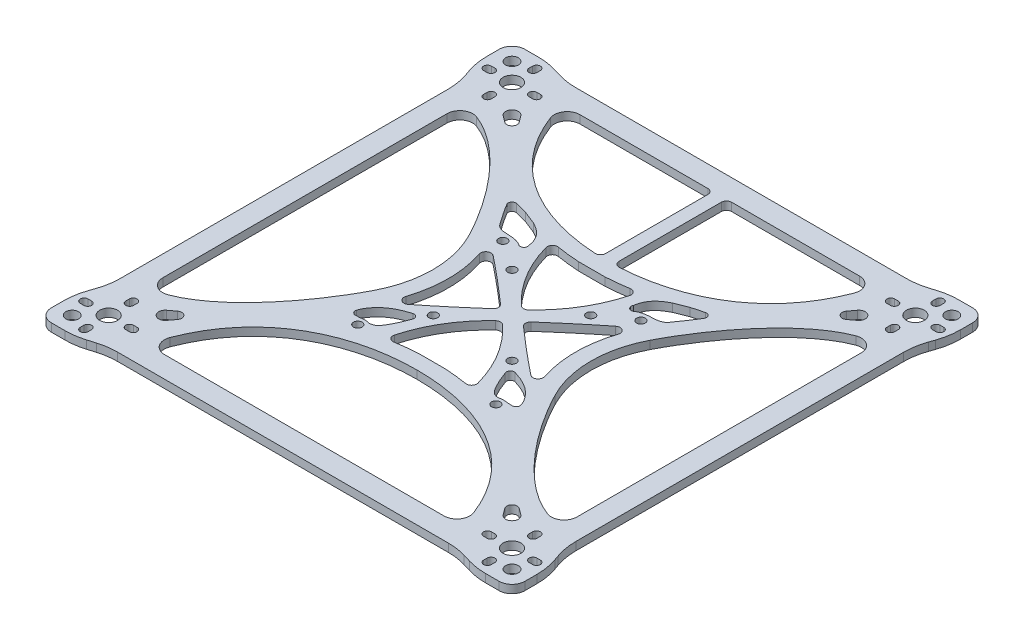
SolidWorks part; units mm, degrees
ref_plane "Front Plane" through (0, 0, 0) normal (0, 0, 1) x (1, 0, 0)
ref_plane "Top Plane" through (0, 0, 0) normal (0, 1, 0) x (1, 0, 0)
ref_plane "Right Plane" through (0, 0, 0) normal (1, 0, 0) x (0, 0, -1)
sketch "Sketch2" plane through (0, 0, 0) normal (0, 1, 0) x (1, 0, 0)
  line L1 (-91.75, 91.75) -> (91.75, 91.75)
  line L2 (-91.75, 91.75) -> (-91.75, -91.75)
  line L3 (-91.75, -91.75) -> (91.75, -91.75)
  line L4 (91.75, 91.75) -> (91.75, -91.75)
  line L5 (-91.75, 91.75) -> (91.75, -91.75) construction
  line L6 (-91.75, -91.75) -> (91.75, 91.75) construction
  point P0 (0, 0)
  dimension "D1" = 183.5
extrude "Base size" add sketch "Sketch2" along normal blind 3.15
sketch "Sketch3" plane through (0, 3.15, 0) normal (0, 1, 0) x (1, 0, 0)
  line L0 (-91.75, 91.75) -> (-91.75, -91.75) construction
  line L1 (80.25, 80.5) -> (-80.25, 80.5)
  line L2 (80.25, 80.5) -> (80.25, -80.5)
  line L3 (80.25, -80.5) -> (-80.25, -80.5)
  line L4 (-80.25, 80.5) -> (-80.25, -80.5)
  line L5 (80.25, 80.5) -> (-80.25, -80.5) construction
  line L6 (80.25, -80.5) -> (-80.25, 80.5) construction
  line L7 (0, 91.75) -> (0, -91.75) construction
  line L8 (-91.75, 0) -> (91.75, 0) construction
  line L9 (-91.75, -88.75) -> (91.75, -88.75)
  line L10 (80.25, 61.3098) -> (-80.25, -61.3098) construction
  line L11 (-91.75, 36.75) -> (91.75, 36.75) construction
  line L12 (88.25, 91.75) -> (88.25, -91.75)
  line L13 (91.75, -91.75) -> (91.75, 91.75) construction
  line L14 (-77.75, 91.75) -> (-67.75, 88.75)
  line L15 (-91.75, 77.75) -> (-88.25, 67.75)
  line L16 (-67.75, 88.75) -> (-67.75, 80.5) construction
  line L17 (-91.75, 88.75) -> (91.75, 88.75)
  line L18 (-88.25, 91.75) -> (-88.25, -91.75)
  line L19 (91.75, 91.75) -> (-91.75, 91.75) construction
  line L20 (-91.75, -91.75) -> (91.75, -91.75) construction
  line L21 (-67.75, 84.625) -> (-77.75, 84.625) construction
  line L22 (-77.75, 91.75) -> (-77.75, 80.5) construction
  line L23 (-91.75, 77.75) -> (-80.25, 77.75) construction
  line L24 (-88.25, 67.75) -> (-80.25, 67.75) construction
  line L25 (-84.25, 67.75) -> (-84.25, 77.75) construction
  line L26 (77.75, 91.75) -> (67.75, 88.75)
  line L27 (91.75, 77.75) -> (88.25, 67.75)
  line L28 (91.75, -77.75) -> (88.25, -67.75)
  line L29 (77.75, -91.75) -> (67.75, -88.75)
  line L30 (-77.75, -91.75) -> (-67.75, -88.75)
  line L31 (-91.75, -77.75) -> (-88.25, -67.75)
  line L32 (-61, 80.5) -> (61, -80.5) construction
  line L33 (61, 80.5) -> (-61, -80.5) construction
  line L34 (0, 36.75) -> (0, -36.75)
  line L35 (-28, 0) -> (28, 0)
  line L36 (2.6, 80.5) -> (2.6, 36.7902)
  line L37 (28, 80.5) -> (28, -91.75) construction
  line L38 (-61, 80.5) -> (61, 80.5) construction
  line L39 (-2.6, 80.5) -> (-2.6, 36.7902)
  line L40 (-80.3099, 61.2501) -> (80.3099, -61.2501) construction
  line L41 (80.25, 61.3098) -> (80.3099, -61.2501) construction
  line L42 (61, 80.5) -> (80.25, 61.3098) construction
  line L43 (-84.25, 77.75) -> (-84.25, 91.75) construction
  line L44 (-77.75, 84.625) -> (-91.75, 84.625) construction
  line L45 (-61, -80.5) -> (-61, -88.75) construction
  line L46 (61, -80.5) -> (61, -88.75) construction
  line L47 (-61, -84.625) -> (61, -84.625) construction
  line L48 (34.054, 44.9401) -> (44.8339, 34.1936) construction
  spline S0 degree 3 poles (61, 80.5) (52.8169, 49.5684) (26.9144, 36.75) (0, 36.75) knots 0 0 0 0 1 1 1 1
  spline S1 degree 3 poles (80.25, 61.3098) (57.9285, 59.6828) (32.235, 20.0435) (28, 0) knots 0 0 0 0 1 1 1 1
  spline S2 degree 3 poles (-61, 80.5) (-52.8169, 49.5684) (-26.9144, 36.75) (0, 36.75) knots 0 0 0 0 1 1 1 1
  spline S3 degree 3 poles (-61, -80.5) (-52.8169, -49.5684) (-26.9144, -36.75) (0, -36.75) knots 0 0 0 0 1 1 1 1
  spline S4 degree 3 poles (61, -80.5) (52.8169, -49.5684) (26.9144, -36.75) (0, -36.75) knots 0 0 0 0 1 1 1 1
  spline S5 degree 3 poles (80.25, -61.3098) (57.9285, -59.6828) (32.235, -20.0435) (28, 0) knots 0 0 0 0 1 1 1 1
  spline S6 degree 3 poles (-80.25, 61.3098) (-57.9285, 59.6828) (-32.235, 20.0435) (-28, 0) knots 0 0 0 0 1 1 1 1
  spline S7 degree 3 poles (-80.25, -61.3098) (-57.9285, -59.6828) (-32.235, -20.0435) (-28, 0) knots 0 0 0 0 1 1 1 1
  point P0 (0, 0)
  point P82 (39.444, 39.5668)
  line M13 (91.75, -91.75) -> (91.75, 91.75)
  line M14 (91.75, 91.75) -> (-91.75, 91.75)
  line M15 (-91.75, 91.75) -> (-91.75, -91.75)
  line M16 (-91.75, -91.75) -> (91.75, -91.75)
  dimension "D2" = 176.5
  dimension "D3" = 177.5
  dimension "D4" = 10
  dimension "D5" = 14
  dimension "D6" = 5.2
  dimension "D7" = 122
  dimension "D8" = 73.5
  dimension "D9" = 8.25
  dimension "D10" = 8
  dimension "D11" = 56
extrude "Base outline and pockets" cut sketch "Sketch3" against normal up to next contours L1 S2 L39 | S0 L1 L36 | L26 L14 L17 M14 | L4 | L2 S1 | L3 S4 S3 | L31 L18 L15 M15 | L30 L29 L9 M16 | L28 L27 L12 M13 region at (26.4341, 3.15, -62.2428) region at (60.1835, 3.15, 0) region at (-26.4341, 3.15, -62.2428) region at (0, 3.15, 62.0397) region at (-60.1835, 3.15, 0) region at (0, 3.15, 90.2844) region at (-90.0401, 3.15, 0) region at (90.0401, 3.15, 0) region at (0, 3.15, -90.2844)
sketch "Sketch4" plane through (0, 3.15, 0) normal (0, 1, 0) x (1, 0, 0)
  line L0 (0, 88.75) -> (0, -88.75) construction
  line L1 (-67.75, 88.75) -> (67.75, 88.75) construction
  line L2 (-67.75, -88.75) -> (67.75, -88.75) construction
  line L3 (-88.25, 0) -> (88.25, 0) construction
  line L4 (-88.25, 67.75) -> (-88.25, -67.75) construction
  line L5 (88.25, 67.75) -> (88.25, -67.75) construction
  line L6 (91.75, 91.75) -> (-91.75, -91.75) construction
  line L7 (-91.75, 91.75) -> (91.75, -91.75) construction
  line L8 (74.6853, 78.1353) -> (81.5853, 78.1353) construction
  line L9 (60.3295, 78.1353) -> (91.8849, 78.1353) construction
  line L10 (91.75, 77.75) -> (88.25, 67.75) construction
  line L11 (78.1353, 91.8656) -> (78.1353, 61.0454) construction
  line L12 (77.75, 91.75) -> (67.75, 88.75) construction
  line L13 (68.6353, 78.1353) -> (70.0103, 78.1353) construction
  line L14 (68.6353, 79.6353) -> (70.0103, 79.6353)
  line L15 (68.6353, 76.6353) -> (70.0103, 76.6353)
  line L16 (71.5103, 78.1353) -> (71.5103, 76.6353) construction
  line L17 (71.5103, 76.6353) -> (67.1353, 76.6353) construction
  line L18 (67.1353, 78.1353) -> (67.1353, 76.6353) construction
  line L19 (87.6353, 78.1353) -> (86.2603, 78.1353) construction
  line L20 (87.6353, 79.6353) -> (86.2603, 79.6353)
  line L21 (87.6353, 76.6353) -> (86.2603, 76.6353)
  line L22 (78.1353, 68.6353) -> (78.1353, 70.0103) construction
  line L23 (79.6353, 68.6353) -> (79.6353, 70.0103)
  line L24 (76.6353, 68.6353) -> (76.6353, 70.0103)
  line L25 (78.1353, 87.6353) -> (78.1353, 86.2603) construction
  line L26 (79.6353, 87.6353) -> (79.6353, 86.2603)
  line L27 (76.6353, 87.6353) -> (76.6353, 86.2603)
  line L28 (-68.6353, 78.1353) -> (-70.0103, 78.1353) construction
  line L29 (-68.6353, 79.6353) -> (-70.0103, 79.6353)
  line L30 (-68.6353, 76.6353) -> (-70.0103, 76.6353)
  line L31 (-78.1353, 87.6353) -> (-78.1353, 86.2603) construction
  line L32 (-79.6353, 87.6353) -> (-79.6353, 86.2603)
  line L33 (-76.6353, 87.6353) -> (-76.6353, 86.2603)
  line L34 (-87.6353, 78.1353) -> (-86.2603, 78.1353) construction
  line L35 (-87.6353, 79.6353) -> (-86.2603, 79.6353)
  line L36 (-87.6353, 76.6353) -> (-86.2603, 76.6353)
  line L37 (-78.1353, 68.6353) -> (-78.1353, 70.0103) construction
  line L38 (-79.6353, 68.6353) -> (-79.6353, 70.0103)
  line L39 (-76.6353, 68.6353) -> (-76.6353, 70.0103)
  line L40 (-87.6353, -78.1353) -> (-86.2603, -78.1353) construction
  line L41 (-87.6353, -79.6353) -> (-86.2603, -79.6353)
  line L42 (-87.6353, -76.6353) -> (-86.2603, -76.6353)
  line L43 (-78.1353, -68.6353) -> (-78.1353, -70.0103) construction
  line L44 (-79.6353, -68.6353) -> (-79.6353, -70.0103)
  line L45 (-76.6353, -68.6353) -> (-76.6353, -70.0103)
  line L46 (-68.6353, -78.1353) -> (-70.0103, -78.1353) construction
  line L47 (-68.6353, -79.6353) -> (-70.0103, -79.6353)
  line L48 (-68.6353, -76.6353) -> (-70.0103, -76.6353)
  line L49 (-78.1353, -87.6353) -> (-78.1353, -86.2603) construction
  line L50 (-79.6353, -87.6353) -> (-79.6353, -86.2603)
  line L51 (-76.6353, -87.6353) -> (-76.6353, -86.2603)
  line L52 (68.6353, -78.1353) -> (70.0103, -78.1353) construction
  line L53 (68.6353, -79.6353) -> (70.0103, -79.6353)
  line L54 (68.6353, -76.6353) -> (70.0103, -76.6353)
  line L55 (78.1353, -87.6353) -> (78.1353, -86.2603) construction
  line L56 (79.6353, -87.6353) -> (79.6353, -86.2603)
  line L57 (76.6353, -87.6353) -> (76.6353, -86.2603)
  line L58 (87.6353, -78.1353) -> (86.2603, -78.1353) construction
  line L59 (87.6353, -79.6353) -> (86.2603, -79.6353)
  line L60 (87.6353, -76.6353) -> (86.2603, -76.6353)
  line L61 (78.1353, -68.6353) -> (78.1353, -70.0103) construction
  line L62 (79.6353, -68.6353) -> (79.6353, -70.0103)
  line L63 (76.6353, -68.6353) -> (76.6353, -70.0103)
  circle A0 centre (78.1353, 78.1353) radius 3.45
  arc A1 (68.6353, 79.6353) -> (68.6353, 76.6353) centre (68.6353, 78.1353) ccw
  arc A2 (70.0103, 76.6353) -> (70.0103, 79.6353) centre (70.0103, 78.1353) ccw
  arc A3 (87.6353, 79.6353) -> (87.6353, 76.6353) centre (87.6353, 78.1353) cw
  arc A4 (86.2603, 76.6353) -> (86.2603, 79.6353) centre (86.2603, 78.1353) cw
  arc A5 (79.6353, 68.6353) -> (76.6353, 68.6353) centre (78.1353, 68.6353) cw
  arc A6 (76.6353, 70.0103) -> (79.6353, 70.0103) centre (78.1353, 70.0103) cw
  arc A7 (79.6353, 87.6353) -> (76.6353, 87.6353) centre (78.1353, 87.6353) ccw
  arc A8 (76.6353, 86.2603) -> (79.6353, 86.2603) centre (78.1353, 86.2603) ccw
  arc A9 (-68.6353, 79.6353) -> (-68.6353, 76.6353) centre (-68.6353, 78.1353) cw
  arc A10 (-70.0103, 76.6353) -> (-70.0103, 79.6353) centre (-70.0103, 78.1353) cw
  arc A11 (-79.6353, 87.6353) -> (-76.6353, 87.6353) centre (-78.1353, 87.6353) cw
  arc A12 (-76.6353, 86.2603) -> (-79.6353, 86.2603) centre (-78.1353, 86.2603) cw
  arc A13 (-87.6353, 79.6353) -> (-87.6353, 76.6353) centre (-87.6353, 78.1353) ccw
  arc A14 (-86.2603, 76.6353) -> (-86.2603, 79.6353) centre (-86.2603, 78.1353) ccw
  arc A15 (-79.6353, 68.6353) -> (-76.6353, 68.6353) centre (-78.1353, 68.6353) ccw
  arc A16 (-76.6353, 70.0103) -> (-79.6353, 70.0103) centre (-78.1353, 70.0103) ccw
  circle A17 centre (-78.1353, 78.1353) radius 3.45
  arc A18 (-87.6353, -79.6353) -> (-87.6353, -76.6353) centre (-87.6353, -78.1353) cw
  arc A19 (-86.2603, -76.6353) -> (-86.2603, -79.6353) centre (-86.2603, -78.1353) cw
  arc A20 (-79.6353, -68.6353) -> (-76.6353, -68.6353) centre (-78.1353, -68.6353) cw
  arc A21 (-76.6353, -70.0103) -> (-79.6353, -70.0103) centre (-78.1353, -70.0103) cw
  arc A22 (-68.6353, -79.6353) -> (-68.6353, -76.6353) centre (-68.6353, -78.1353) ccw
  arc A23 (-70.0103, -76.6353) -> (-70.0103, -79.6353) centre (-70.0103, -78.1353) ccw
  arc A24 (-79.6353, -87.6353) -> (-76.6353, -87.6353) centre (-78.1353, -87.6353) ccw
  arc A25 (-76.6353, -86.2603) -> (-79.6353, -86.2603) centre (-78.1353, -86.2603) ccw
  arc A26 (68.6353, -79.6353) -> (68.6353, -76.6353) centre (68.6353, -78.1353) cw
  arc A27 (70.0103, -76.6353) -> (70.0103, -79.6353) centre (70.0103, -78.1353) cw
  arc A28 (79.6353, -87.6353) -> (76.6353, -87.6353) centre (78.1353, -87.6353) cw
  arc A29 (76.6353, -86.2603) -> (79.6353, -86.2603) centre (78.1353, -86.2603) cw
  arc A30 (87.6353, -79.6353) -> (87.6353, -76.6353) centre (87.6353, -78.1353) ccw
  arc A31 (86.2603, -76.6353) -> (86.2603, -79.6353) centre (86.2603, -78.1353) ccw
  arc A32 (79.6353, -68.6353) -> (76.6353, -68.6353) centre (78.1353, -68.6353) ccw
  arc A33 (76.6353, -70.0103) -> (79.6353, -70.0103) centre (78.1353, -70.0103) ccw
  circle A34 centre (78.1353, -78.1353) radius 3.45
  circle A35 centre (-78.1353, -78.1353) radius 3.45
  spline S0 degree 3 poles (61, 80.5) (53.0808, 50.5659) (28.5665, 37.5955) (2.6, 36.7902) knots 0 0 0 0 0.967753 0.967753 0.967753 0.967753 construction
  spline S1 degree 3 poles (80.25, 61.3098) (57.9285, 59.6828) (32.235, 20.0435) (28, 0) knots 0 0 0 0 1 1 1 1 construction
  point P26 (64.677, 77.75)
  point P29 (0, 0)
  point P42 (69.3228, 78.1353)
  point P53 (86.9478, 78.1353)
  point P60 (78.1353, 69.3228)
  point P67 (78.1353, 86.9478)
  point P74 (-69.3228, 78.1353)
  point P81 (-78.1353, 86.9478)
  point P88 (-86.9478, 78.1353)
  point P95 (-78.1353, 69.3228)
  point P104 (-86.9478, -78.1353)
  point P111 (-78.1353, -69.3228)
  point P118 (-69.3228, -78.1353)
  point P125 (-78.1353, -86.9478)
  point P132 (69.3228, -78.1353)
  point P139 (78.1353, -86.9478)
  point P146 (86.9478, -78.1353)
  point P153 (78.1353, -69.3228)
  point P162 (59.9091, 77.65)
  point P163 (59.9091, 77.65)
  point P164 (0, 0)
  point P165 (0, 0)
  point P166 (0, 0)
  point P167 (0, 0)
  point P168 (0, 0)
  point P169 (91.75, 91.75)
  point P170 (91.75, 91.75)
  point P171 (0, 0)
  point P172 (0, 0)
  dimension "D1" = 6.9
  dimension "D5" = 1.5
  dimension "D2" = 221
  dimension "D3" = 13.25
  dimension "D4" = 22
extrude "Motor holes" cut sketch "Sketch4" against normal up to next
sketch "Sketch5" plane through (0, 3.15, 0) normal (0, 1, 0) x (1, 0, 0)
  line L0 (-91.75, -91.75) -> (91.75, 91.75) construction
  line L1 (-91.75, 91.75) -> (91.75, -91.75) construction
  line L2 (-28, 0) -> (28, 0) construction
  line L3 (0, 88.75) -> (0, -88.75) construction
  line L4 (-26.75, 23.1997) -> (26.75, 23.1997)
  line L5 (-26.75, 23.1997) -> (-26.75, -33.0003)
  line L6 (-26.75, -33.0003) -> (26.75, -33.0003)
  line L7 (26.75, 23.1997) -> (26.75, -33.0003)
  line L8 (-26.75, 23.1997) -> (26.75, -33.0003) construction
  line L9 (-26.75, -33.0003) -> (26.75, 23.1997) construction
  line L10 (-67.75, 88.75) -> (67.75, 88.75) construction
  line L11 (-67.75, -88.75) -> (67.75, -88.75) construction
  line L12 (16.1608, -16.6558) -> (25.8392, -31.5945)
  line L13 (15.25, -15.25) -> (26.75, -33.0003) construction
  circle A0 centre (15.25, 15.25) radius 1.675
  circle A1 centre (-15.25, -15.25) radius 1.675
  circle A2 centre (-15.25, 15.25) radius 1.675
  circle A3 centre (15.25, -15.25) radius 1.675
  circle A4 centre (-26.75, 23.1997) radius 1.675
  circle A5 centre (26.75, 23.1997) radius 1.675
  circle A6 centre (26.75, -33.0003) radius 1.675
  circle A7 centre (-26.75, -33.0003) radius 1.675
  point P20 (0, -4.9003)
  dimension "D1" = 3.35
  dimension "D2" = 30.5
  dimension "D3" = 53.5
  dimension "D4" = 56.2
  dimension "D5" = 17.8
extrude "FC holes" cut sketch "Sketch5" against normal up to next contours L4 A4 L5 | L5 A4 L4 | A2 | A0 | L7 A5 L4 | L4 A5 L7 | L6 A6 L7 | L7 A6 L6 | A3 | A1 | L5 A7 L6 | L6 A7 L5 region at (-26.987, 3.15, -23.4367) region at (-26.0391, 3.15, -22.4888) region at (15.25, 3.15, 15.25) region at (26.987, 3.15, -23.4367) region at (26.0391, 3.15, -22.4888) region at (-26.0391, 3.15, 32.2894) region at (-26.987, 3.15, 33.2372) region at (26.987, 3.15, 33.2372) region at (26.0391, 3.15, 32.2894) region at (15.25, 3.15, -15.25) region at (-15.25, 3.15, 15.25) region at (-15.25, 3.15, -15.25)
sketch "Sketch6" plane through (0, 3.15, 0) normal (0, 1, 0) x (1, 0, 0)
  line L0 (-91.75, 91.75) -> (91.75, -91.75) construction
  line L1 (-91.75, -91.75) -> (91.75, 91.75) construction
  line L2 (0, 88.75) -> (0, -88.75) construction
  line L3 (-67.75, 88.75) -> (67.75, 88.75) construction
  line L4 (-67.75, -88.75) -> (67.75, -88.75) construction
  line L5 (-88.25, 0) -> (88.25, 0) construction
  line L6 (-88.25, 67.75) -> (-88.25, -67.75) construction
  line L7 (88.25, 67.75) -> (88.25, -67.75) construction
  line L8 (63.5689, 63.5689) -> (68.9429, 68.9429) construction
  line L9 (65.2484, 68.6777) -> (63.3814, 66.1808)
  line L10 (66.1808, 63.3814) -> (68.6777, 65.2484)
  line L11 (-63.3814, -66.1808) -> (-65.2484, -68.6777)
  line L12 (-68.6777, -65.2484) -> (-66.1808, -63.3814)
  line L13 (65.2484, -68.6777) -> (63.3814, -66.1808)
  line L14 (66.1808, -63.3814) -> (68.6777, -65.2484)
  line L15 (-68.6777, 65.2484) -> (-66.1808, 63.3814)
  line L16 (-63.3814, 66.1808) -> (-65.2484, 68.6777)
  circle A0 centre (-85.2064, 85.2064) radius 2.45
  circle A1 centre (85.2064, 85.2064) radius 2.45
  circle A2 centre (85.2064, -85.2064) radius 2.45
  circle A3 centre (-85.2064, -85.2064) radius 2.45
  circle A4 centre (67.2105, 67.2105) radius 2.45
  circle A5 centre (64.9831, 64.9831) radius 2
  circle A6 centre (-64.9831, -64.9831) radius 2
  circle A7 centre (-67.2105, -67.2105) radius 2.45
  circle A8 centre (67.2105, -67.2105) radius 2.45
  circle A9 centre (64.9831, -64.9831) radius 2
  circle A10 centre (-64.9831, 64.9831) radius 2
  circle A11 centre (-67.2105, 67.2105) radius 2.45
  circle A12 centre (78.1353, 78.1353) radius 3.45 construction
  dimension "D1" = 4.9
  dimension "D3" = 7.6
  dimension "D4" = 4
  dimension "D2" = 10
  dimension "D5" = 195
extrude "Motor wire holes" cut sketch "Sketch6" against normal up to next contours A0 | A10 A11 | A10 A11 | A11 A10 | A1 | A5 A4 | A4 A5 | A5 A4 | A2 | A8 A9 | A9 A8 | A9 A8 | L14 A9 A8 | A8 A9 L13 | A3 | A7 A6 | A6 A7 | A7 A6 | L12 A7 A6 | A6 A7 L11 | A11 L15 A10 | A11 A10 L16 | A5 A4 L9 | A5 L10 A4 region at (64.438, 3.15, -67.2832) region at (67.4336, 3.15, -67.4336) region at (64.7131, 3.15, -64.7131) region at (65.9277, 3.15, -65.9277) region at (67.2832, 3.15, -64.438) region at (-64.7131, 3.15, 64.7131) region at (-64.438, 3.15, 67.2832) region at (-67.4336, 3.15, 67.4336) region at (-65.9277, 3.15, 65.9277) region at (-67.2832, 3.15, 64.438) region at (67.4336, 3.15, 67.4336) region at (64.438, 3.15, 67.2832) region at (64.7131, 3.15, 64.7131) region at (65.9277, 3.15, 65.9277) region at (67.2832, 3.15, 64.438) region at (-67.2832, 3.15, -64.438) region at (-67.4336, 3.15, -67.4336) region at (-64.7131, 3.15, -64.7131) region at (-64.438, 3.15, -67.2832) region at (-65.9277, 3.15, -65.9277) region at (-85.2064, 3.15, -85.2064) region at (85.2064, 3.15, -85.2064) region at (85.2064, 3.15, 85.2064) region at (-85.2064, 3.15, 85.2064)
fillet "Large pocket fillet" radius 40 2 edges at (28, 1.575, 0) (-28, 1.575, 0)
fillet "Outside edge fillet" radius 25 16 edges at (-88.25, 1.575, 67.75) (-91.75, 1.575, 77.75) (-88.25, 1.575, -67.75) (-91.75, 1.575, -77.75) (-77.75, 1.575, -91.75) (-67.75, 1.575, -88.75) (67.75, 1.575, -88.75) (77.75, 1.575, -91.75) (91.75, 1.575, -77.75) (88.25, 1.575, -67.75) (88.25, 1.575, 67.75) (91.75, 1.575, 77.75) (77.75, 1.575, 91.75) (67.75, 1.575, 88.75) (-67.75, 1.575, 88.75) (-77.75, 1.575, 91.75)
fillet "Inner pocket fillet" radius 5 12 edges at (80.25, 1.575, 61.3098) (80.25, 1.575, -61.3098) (-80.25, 1.575, 61.3098) (-80.25, 1.575, -61.3098) (-61, 1.575, 80.5) (61, 1.575, 80.5) (61, 1.575, -80.5) (-61, 1.575, -80.5) (-91.75, 1.575, -91.75) (91.75, 1.575, -91.75) (91.75, 1.575, 91.75) (-91.75, 1.575, 91.75)
fillet "Small pocket fillet" radius 2 4 edges at (-2.6, 1.575, -36.7902) (2.6, 1.575, -36.7902) (2.6, 1.575, -80.5) (-2.6, 1.575, -80.5)
sketch "Sketch7" plane through (0, 3.15, 0) normal (0, 1, 0) x (1, 0, 0)
  line L0 (-16.925, 38.5516) -> (-16.925, -38.5516) construction
  line L1 (0, 88.75) -> (0, -88.75) construction
  line L2 (-64.0808, 88.75) -> (64.0808, 88.75) construction
  line L3 (-64.0808, -88.75) -> (64.0808, -88.75) construction
  line L4 (-88.25, 0) -> (88.25, 0) construction
  line L5 (-88.25, 63.5014) -> (-88.25, -63.5014) construction
  line L6 (88.25, 63.5014) -> (88.25, -63.5014) construction
  line L7 (-5.0538, 30.8925) -> (5.0538, 30.8925)
  line L8 (-90.2855, -90.2855) -> (90.2855, 90.2855) construction
  line L9 (90.2855, -90.2855) -> (-90.2855, 90.2855) construction
  line L10 (-16.925, 10.8936) -> (-10.9183, 16.9003) construction
  line L11 (-4.25, 3.75) -> (4.25, 3.75)
  line L12 (-4.25, 3.75) -> (-4.25, -3.75)
  line L13 (-4.25, -3.75) -> (4.25, -3.75)
  line L14 (4.25, 3.75) -> (4.25, -3.75)
  line L15 (-4.25, 3.75) -> (4.25, -3.75) construction
  line L16 (-4.25, -3.75) -> (4.25, 3.75) construction
  line L17 (-5.0538, -30.8925) -> (5.0538, -30.8925)
  line L20 (-34.8215, 16.925) -> (34.391, 16.925) construction
  line L21 (15.25, 15.25) -> (15.25, -15.25) construction
  line L22 (90.2855, 90.2855) -> (-88.25, -12.0526) construction
  line L23 (-88.25, 63.5014) -> (-88.25, -63.5014) construction
  line L24 (-26.75, 23.1997) -> (26.75, 23.1997) construction
  line L25 (-88.25, 36.8829) -> (88.25, 36.8829) construction
  line L26 (88.25, 63.5014) -> (88.25, -63.5014) construction
  circle A0 centre (-21.5445, 26.1835) radius 1.5
  circle A1 centre (-15.25, 15.25) radius 1.675 construction
  arc A2 (29.7964, -21.1732) -> (29.7964, 21.1732) centre (70.6339, 0) cw
  arc A3 (-29.7964, -21.1732) -> (-29.7964, 21.1732) centre (-70.6339, 0) ccw
  arc A4 (-29.7964, -21.1732) -> (-29.7964, 21.1732) centre (-70.6339, 0) ccw
  arc A5 (-91.75, -86.75) -> (-86.75, -91.75) centre (-86.75, -86.75) ccw construction
  arc A6 (91.75, 86.75) -> (86.75, 91.75) centre (86.75, 86.75) ccw construction
  arc A7 (86.75, -91.75) -> (91.75, -86.75) centre (86.75, -86.75) ccw construction
  arc A8 (-86.75, 91.75) -> (-91.75, 86.75) centre (-86.75, 86.75) ccw construction
  circle A9 centre (-36.9396, 36.9396) radius 1.5
  circle A10 centre (21.5445, 26.1835) radius 1.5
  circle A11 centre (36.9396, 36.9396) radius 1.5
  circle A12 centre (-19.4019, -20.031) radius 1.5
  circle A13 centre (-30.4025, -28.806) radius 1.5
  circle A14 centre (19.4019, -20.031) radius 1.5
  circle A15 centre (30.4025, -28.806) radius 1.5
  arc A20 (35.1231, 18.4115) -> (35.1231, -18.4115) centre (70.6339, 0) ccw construction
  spline S0 degree 3 poles (1646.3229, 1054.028) (81.128, 560.1113) (-122.2034, 169.5598) (-58.2555, 59.2518) (-56.365, 56.5397) (-52.2443, 51.5404) (-50.0144, 49.2533) (-45.2746, 45.1018) (-42.7649, 43.2373) (-34.9047, 38.2598) (-29.2265, 35.7639) (128.467, -11.0091) (434.3868, 432.3515) (-1986.9742, -2.3886) knots -4.46889 -4.46889 -4.46889 -4.46889 0.125 0.125 0.25 0.25 0.375 0.375 0.5 0.5 0.75 0.75 7.170137 7.170137 7.170137 7.170137 only from (-64.4192, 71.565) to (-5.0538, 30.8925)
  spline S1 degree 3 poles (-64.4192, 71.565) (-63.1407, 68.2274) (-61.6434, 65.0957) (-58.2555, 59.2518) (-56.365, 56.5397) (-52.2443, 51.5404) (-50.0144, 49.2533) (-45.2746, 45.1018) (-42.7649, 43.2373) (-34.9047, 38.2598) (-29.2265, 35.7639) (-17.4057, 32.2577) (-11.2615, 31.2452) (-5.0538, 30.8925) knots 0 0 0 0 0.125 0.125 0.25 0.25 0.375 0.375 0.5 0.5 0.75 0.75 1 1 1 1
  spline S2 degree 3 poles (64.4192, 71.565) (63.1407, 68.2274) (61.6434, 65.0957) (58.2555, 59.2518) (56.365, 56.5397) (52.2443, 51.5404) (50.0144, 49.2533) (45.2746, 45.1018) (42.7649, 43.2373) (34.9047, 38.2598) (29.2265, 35.7639) (17.4057, 32.2577) (11.2615, 31.2452) (5.0538, 30.8925) knots 0 0 0 0 0.125 0.125 0.25 0.25 0.375 0.375 0.5 0.5 0.75 0.75 1 1 1 1
  spline S3 degree 2 poles (-16.925, 32.417) (-13.1474, 15.3314) (0, 3.75) knots 0 0 0 1 1 1
  spline S4 degree 3 poles (64.4192, -71.565) (63.1407, -68.2274) (61.6434, -65.0957) (58.2555, -59.2518) (56.365, -56.5397) (52.2443, -51.5404) (50.0144, -49.2533) (45.2746, -45.1018) (42.7649, -43.2373) (34.9047, -38.2598) (29.2265, -35.7639) (17.4057, -32.2577) (11.2615, -31.2452) (5.0538, -30.8925) knots 0 0 0 0 0.125 0.125 0.25 0.25 0.375 0.375 0.5 0.5 0.75 0.75 1 1 1 1
  spline S5 degree 3 poles (-64.4192, -71.565) (-63.1407, -68.2274) (-61.6434, -65.0957) (-58.2555, -59.2518) (-56.365, -56.5397) (-52.2443, -51.5404) (-50.0144, -49.2533) (-45.2746, -45.1018) (-42.7649, -43.2373) (-34.9047, -38.2598) (-29.2265, -35.7639) (-17.4057, -32.2577) (-11.2615, -31.2452) (-5.0538, -30.8925) knots 0 0 0 0 0.125 0.125 0.25 0.25 0.375 0.375 0.5 0.5 0.75 0.75 1 1 1 1
  spline S8 degree 3 poles (-1134.0161, 1685.3643) (-49.3729, -207.5723) (26.6814, -60.6672) (-40.7855, 39.0077) (-44.0849, 43.3226) (-49.3783, 49.2973) (-51.2004, 51.206) (-54.9484, 54.8014) (-56.8742, 56.4883) (-60.8255, 59.5815) (-62.8511, 60.988) (-130.4494, 101.0329) (-249.7376, -33.0626) (-622.9532, -1852.5469) knots -5.128274 -5.128274 -5.128274 -5.128274 0.25 0.25 0.5 0.5 0.625 0.625 0.75 0.75 0.875 0.875 4.813958 4.813958 4.813958 4.813958 only from (-29.7964, 21.1732) to (-71.3367, 65.3441)
  spline S9 degree 3 poles (-622.9539, 1852.5503) (-249.7378, 33.0628) (-130.4494, -101.0329) (-62.8511, -60.988) (-60.8255, -59.5815) (-56.8742, -56.4883) (-54.9484, -54.8014) (-51.2004, -51.206) (-49.3783, -49.2973) (-44.0849, -43.3226) (-40.7855, -39.0077) (26.6809, 60.6663) (-49.3716, 207.5698) (-1133.9881, -1685.3155) knots -3.81396 -3.81396 -3.81396 -3.81396 0.125 0.125 0.25 0.25 0.375 0.375 0.5 0.5 0.75 0.75 6.128227 6.128227 6.128227 6.128227 only from (-71.3367, -65.3441) to (-29.7964, -21.1732)
  spline S10 degree 3 poles (-29.7964, 21.1732) (-32.0988, 25.6138) (-34.7919, 30.1529) (-40.7855, 39.0077) (-44.0849, 43.3226) (-49.3783, 49.2973) (-51.2004, 51.206) (-54.9484, 54.8014) (-56.8742, 56.4883) (-60.8255, 59.5815) (-62.8511, 60.988) (-67.0095, 63.4515) (-69.1429, 64.509) (-71.3367, 65.3441) knots 0 0 0 0 0.25 0.25 0.5 0.5 0.625 0.625 0.75 0.75 0.875 0.875 1 1 1 1
  spline S11 degree 3 poles (-71.3367, -65.3441) (-69.1429, -64.509) (-67.0095, -63.4515) (-62.8511, -60.988) (-60.8255, -59.5815) (-56.8742, -56.4883) (-54.9484, -54.8014) (-51.2004, -51.206) (-49.3783, -49.2973) (-44.0849, -43.3226) (-40.7855, -39.0077) (-34.7919, -30.1529) (-32.0988, -25.6138) (-29.7964, -21.1732) knots 0 0 0 0 0.125 0.125 0.25 0.25 0.375 0.375 0.5 0.5 0.75 0.75 1 1 1 1
  spline S12 degree 3 poles (71.3367, -65.3441) (69.1429, -64.509) (67.0095, -63.4515) (62.8511, -60.988) (60.8255, -59.5815) (56.8742, -56.4883) (54.9484, -54.8014) (51.2004, -51.206) (49.3783, -49.2973) (44.0849, -43.3226) (40.7855, -39.0077) (34.7919, -30.1529) (32.0988, -25.6138) (29.7964, -21.1732) knots 0 0 0 0 0.125 0.125 0.25 0.25 0.375 0.375 0.5 0.5 0.75 0.75 1 1 1 1
  spline S13 degree 3 poles (29.7964, 21.1732) (32.0988, 25.6138) (34.7919, 30.1529) (40.7855, 39.0077) (44.0849, 43.3226) (49.3783, 49.2973) (51.2004, 51.206) (54.9484, 54.8014) (56.8742, 56.4883) (60.8255, 59.5815) (62.8511, 60.988) (67.0095, 63.4515) (69.1429, 64.509) (71.3367, 65.3441) knots 0 0 0 0 0.25 0.25 0.5 0.5 0.625 0.625 0.75 0.75 0.875 0.875 1 1 1 1
  spline S14 degree 2 poles (-4.25, 0) (-16.6416, 11.0472) (-29.7964, 21.1732) knots 0 0 0 1 1 1
  spline S15 degree 2 poles (-4.25, 0) (-16.6416, -11.0472) (-29.7964, -21.1732) knots 0 0 0 1 1 1
  spline S16 degree 2 poles (4.25, 0) (16.6416, 11.0472) (29.7964, 21.1732) knots 0 0 0 1 1 1
  spline S17 degree 2 poles (4.25, 0) (16.6416, -11.0472) (29.7964, -21.1732) knots 0 0 0 1 1 1
  spline S18 degree 3 poles (-21.9791, 24.7479) (-23.5878, 25.961) (-26.3725, 26.354) (-29.9957, 26.3605) (-32.2323, 27.1662) (-34.8801, 31.1932) (-36.8125, 33.6901) (-38.3665, 36.4772) knots 0 0 0 0 0.266776 0.366283 0.496008 0.55938 1 1 1 1
  spline S19 degree 3 poles (-20.2432, 26.9295) (-20.8297, 31.2566) (-26.2951, 35.6787) (-33.5009, 37.7311) (-36.6227, 38.4057) knots 0 0 0 0 0.515354 1 1 1 1
  spline S20 degree 3 poles (20.2432, 26.9295) (20.8297, 31.2566) (26.2951, 35.6787) (33.5009, 37.7311) (36.6227, 38.4057) knots 0 0 0 0 0.515354 1 1 1 1
  spline S21 degree 3 poles (21.9791, 24.7479) (23.5878, 25.961) (26.3725, 26.354) (29.9957, 26.3605) (32.2323, 27.1662) (34.8801, 31.1932) (36.8125, 33.6901) (38.3665, 36.4772) knots 0 0 0 0 0.266776 0.366283 0.496008 0.55938 1 1 1 1
  spline S22 degree 3 poles (-19.8388, -18.5961) (-22.3686, -19.3665) (-27.6569, -21.3902) (-31.4613, -26.6871) (-31.8655, -28.4753) knots 0 0 0 0 0.555172 1 1 1 1
  spline S23 degree 3 poles (-18.0503, -20.6816) (-18.9124, -23.2799) (-21.0529, -28.0893) (-23.1479, -30.0025) (-25.0795, -30.4588) (-26.0674, -30.0052) (-27.5923, -30.0995) (-29.0445, -30.305) (-29.8811, -30.306) (-30.4025, -30.306) knots 0 0 0 0 0.491044 0.606921 0.658583 0.729368 0.792681 0.893562 1 1 1 1
  spline S24 degree 3 poles (18.0503, -20.6816) (18.9124, -23.2799) (21.0529, -28.0893) (23.1479, -30.0025) (25.0795, -30.4588) (26.0674, -30.0052) (27.5923, -30.0995) (29.0445, -30.305) (29.8811, -30.306) (30.4025, -30.306) knots 0 0 0 0 0.491044 0.606921 0.658583 0.729368 0.792681 0.893562 1 1 1 1
  spline S25 degree 3 poles (19.8388, -18.5961) (22.3686, -19.3665) (27.6569, -21.3902) (31.4613, -26.6871) (31.8655, -28.4753) knots 0 0 0 0 0.555172 1 1 1 1
  spline S26 degree 2 poles (16.925, 32.417) (13.1474, 15.3314) (0, 3.75) knots 0 0 0 1 1 1
  spline S27 degree 2 poles (-16.925, -32.417) (-13.1474, -15.3314) (0, -3.75) knots 0 0 0 1 1 1
  spline S28 degree 2 poles (16.925, -32.417) (13.1474, -15.3314) (0, -3.75) knots 0 0 0 1 1 1
  spline S30 degree 3 poles (-58.8163, 73.7114) (-49.4768, 49.3311) (-27.8394, 38.1967) (-4.7134, 36.8829) knots 0.076565 0.076565 0.076565 0.076565 0.941454 0.941454 0.941454 0.941454 construction
  spline S31 degree 3 poles (-58.8163, -73.7114) (-48.8446, -47.6807) (-24.8537, -36.75) (0, -36.75) knots 0.076565 0.076565 0.076565 0.076565 1 1 1 1 construction
  point P33 (16.925, -32.4171)
  point P63 (0, 0)
  point P73 (-16.925, -32.4169)
  point P74 (0, 0)
  point P78 (0, 0)
  point P79 (0, 0)
  point P80 (0, 0)
  point P81 (0, 0)
  point P84 (0, 0)
  point P122 (0, 0)
  point P130 (0, 0)
  point P142 (0, 0)
  point P149 (-34.8215, 16.9003)
  point P151 (0, 0)
  point P169 (-21.9791, -28.806)
  point P170 (0, 0)
  point P171 (0, 0)
  dimension "D5" = 8.5
  dimension "D6" = 7.5
  dimension "D7" = 3
  dimension "D8" = 6
  dimension "D1" = 6
  dimension "D4" = 6
extrude "Inner pockets" cut sketch "Sketch7" against normal up to next contours S23 A12 S22 A13 | A13 | A12 | S18 A9 | A0 S19 S1 A9 S18 | S18 A0 | A11 S21 | A10 S21 A11 S20 S2 | A10 S21 | A14 | S25 A14 S24 A15 | A15 | S26 S2 L7 S1 S3 | S16 S17 A2 | S4 S28 S27 S5 L17 | S15 S14 A4 region at (0, 3.15, -21.1528) region at (-29.0578, 3.15, -31.4939) region at (29.0578, 3.15, -31.4944) region at (-21.5398, 3.15, -26.1908) region at (21.5398, 3.15, -26.1908) region at (-36.9374, 3.15, -36.9408) region at (-18.8047, 3.15, 0) region at (18.8047, 3.15, 0) region at (36.9374, 3.15, -36.9408) region at (0, 3.15, 21.1528) region at (-19.4019, 3.15, 20.031) region at (-18.4002, 3.15, 18.6789) region at (-24.6165, 3.15, 25.1257) region at (19.4019, 3.15, 20.031) region at (25.0559, 3.15, 25.4051)
fillet "Pocket fillet" radius 2 12 edges at (29.7964, 1.575, 21.1732) (-29.7964, 1.575, 21.1732) (4.25, 1.575, 0) (29.7964, 1.575, -21.1732) (-4.25, 1.575, 0) (-29.7964, 1.575, -21.1732) (0, 1.575, 3.75) (0, 1.575, -3.75)
sketch "Sketch8" plane through (0, 3.15, 0) normal (0, 1, 0) x (1, 0, 0)
  line L0 (-86.75, -91.75) -> (-81.4192, -91.75) construction
  line L1 (-91.75, 91.75) -> (0, 91.75)
  line L2 (-91.75, 91.75) -> (-91.75, -91.75)
  line L3 (-91.75, -91.75) -> (0, -91.75)
  line L4 (0, 91.75) -> (0, -91.75)
  line L5 (-91.75, -81.9986) -> (-91.75, -86.75) construction
extrude "Cut-Extrude6" [suppressed] cut sketch "Sketch8" against normal up to next
sketch "Sketch9" plane through (0, 3.15, 0) normal (0, 1, 0) x (1, 0, 0)
  line L0 (86.75, 91.75) -> (81.4192, 91.75) construction
  line L1 (91.75, 91.75) -> (0, 91.75)
  line L2 (91.75, 91.75) -> (91.75, -91.75)
  line L3 (91.75, -91.75) -> (0, -91.75)
  line L4 (0, 91.75) -> (0, -91.75)
  line L5 (91.75, 81.9986) -> (91.75, 86.75) construction
extrude "Cut-Extrude7" [suppressed] cut sketch "Sketch9" against normal offset from surface (2.65 mm away) 0.5 up to face at (-21.612, 0, 0)
